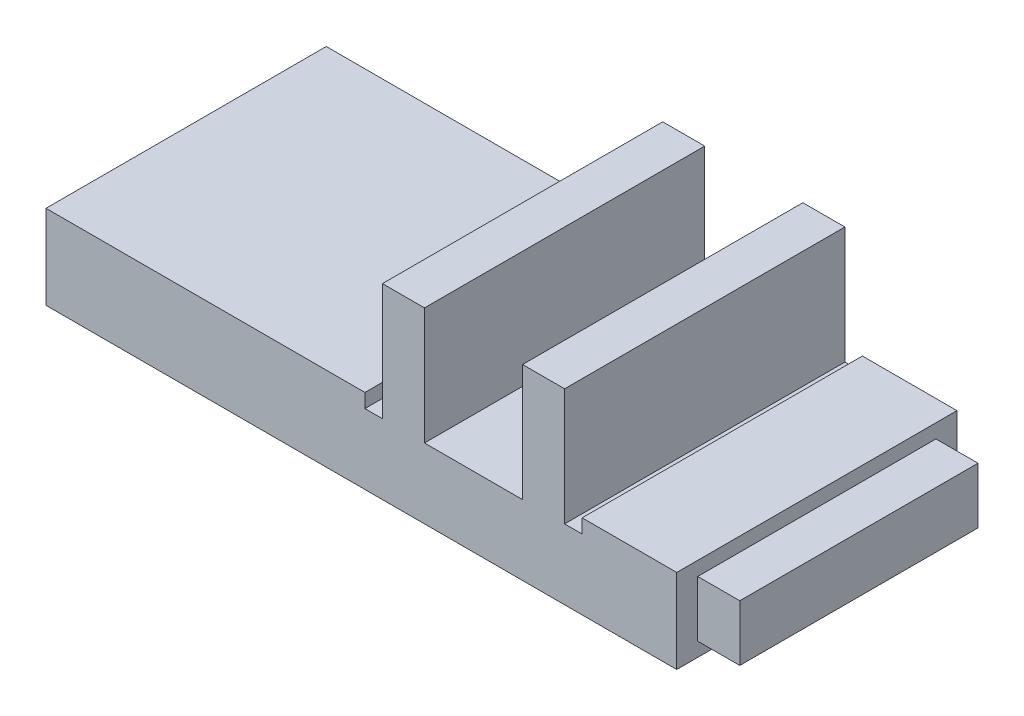
SolidWorks part; units mm, degrees
ref_plane "Front Plane" through (0, 0, 0) normal (0, 0, 1) x (1, 0, 0)
ref_plane "Top Plane" through (0, 0, 0) normal (0, 1, 0) x (1, 0, 0)
ref_plane "Right Plane" through (0, 0, 0) normal (1, 0, 0) x (0, 0, -1)
sketch "Sketch2" plane through (0, 0, 0) normal (0, 0, 1) x (1, 0, 0)
  line L0 (-7.75, 1) -> (-30.51, 1)
  line L1 (-30.51, 1) -> (-30.51, -5)
  line L2 (-30.51, -5) -> (14.5, -5)
  line L3 (14.5, -5) -> (14.5, 1)
  line L4 (14.5, 1) -> (7.75, 1)
  line L5 (7.75, 1) -> (7.75, 0)
  line L6 (7.75, 0) -> (-7.75, 0)
  line L7 (-7.75, 0) -> (-7.75, 1)
  point P2 (0, 0)
  dimension "D1" = 22.76
  dimension "D2" = 5
  dimension "D3" = 1
  dimension "D4" = 15.5
  dimension "D5" = 6.75
extrude "Boss-Extrude1" add sketch "Sketch2" along normal blind 20
sketch "Sketch6" plane through (14.5, 0, 0) normal (1, 0, 0) x (0, 0, -1)
  line L0 (-20, 1) -> (0, 1) construction
  line L1 (-18.5, 0) -> (-1.5, 0)
  line L2 (-18.5, 0) -> (-18.5, -4)
  line L3 (-18.5, -4) -> (-1.5, -4)
  line L4 (-1.5, 0) -> (-1.5, -4)
  line L5 (-18.5, 0) -> (-1.5, -4) construction
  line L6 (-18.5, -4) -> (-1.5, 0) construction
  line L7 (0, -5) -> (0, 1) construction
  point P0 (-10, -2)
  point P9 (-10, 1)
  point P12 (0, -2)
  dimension "D1" = 4
  dimension "D2" = 17
extrude "Boss-Extrude3" add sketch "Sketch6" along normal blind 3
sketch "Sketch7" plane through (0, 0, 0) normal (0, 1, 0) x (1, 0, 0)
  line L1 (-6.5, 0) -> (-3.5, 0)
  line L2 (-6.5, 0) -> (-6.5, -20)
  line L3 (-6.5, -20) -> (-3.5, -20)
  line L4 (-3.5, 0) -> (-3.5, -20)
  line L5 (-6.5, 0) -> (-3.5, -20) construction
  line L6 (-6.5, -20) -> (-3.5, 0) construction
  line L10 (7.75, 0) -> (-7.75, 0) construction
  line L11 (7.75, -20) -> (-7.75, -20) construction
  line L13 (0, 0) -> (0, -20) construction
  line L14 (6.5, -20) -> (3.5, -20)
  line L15 (3.5, 0) -> (3.5, -20)
  line L16 (6.5, 0) -> (6.5, -20)
  line L17 (6.5, 0) -> (3.5, 0)
  line L18 (-7.75, -20) -> (-7.75, 0) construction
  point P0 (-5, -10)
  dimension "D1" = 3
  dimension "D2" = 1.25
extrude "Boss-Extrude4" add sketch "Sketch7" along normal blind 8.35
